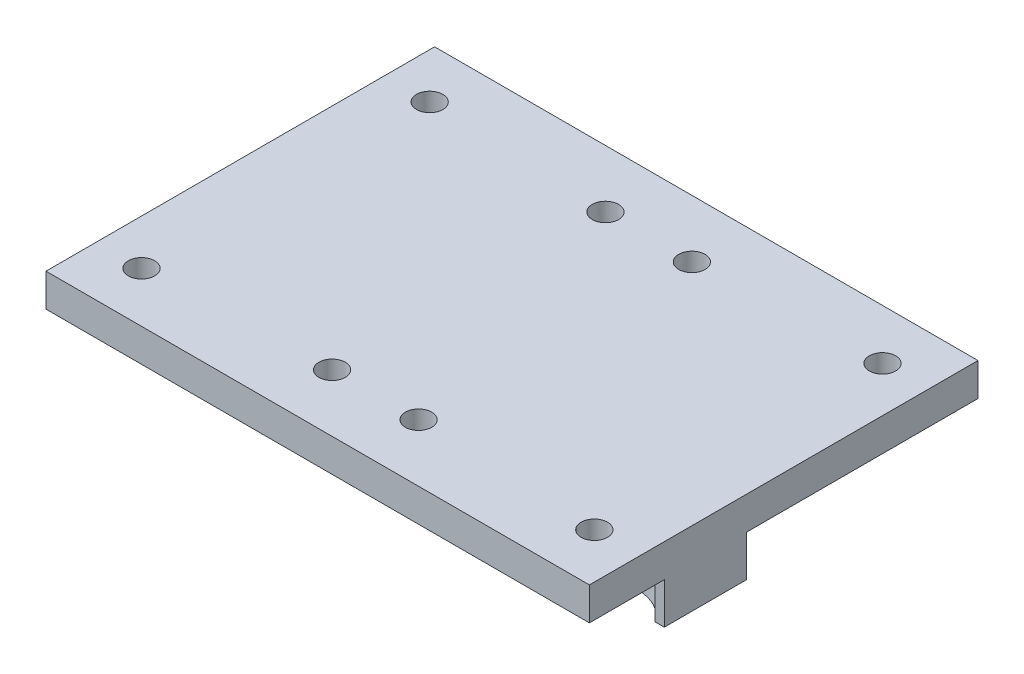
SolidWorks part; units mm, degrees
ref_plane "前视基准面" through (0, 0, 0) normal (0, 0, 1) x (1, 0, 0)
ref_plane "上视基准面" through (0, 0, 0) normal (0, 1, 0) x (1, 0, 0)
ref_plane "右视基准面" through (0, 0, 0) normal (1, 0, 0) x (0, 0, -1)
other "Configuration Table"
sketch "草图7" plane through (0, 0, 0) normal (0, 1, 0) x (1, 0, 0)
  line L21 (0, 23.6) -> (0, -23.6) construction
  line L22 (-33, 23.6) -> (33, 23.6)
  line L23 (-33, 23.6) -> (-33, -23.6)
  line L24 (-33, -23.6) -> (33, -23.6)
  line L25 (33, 23.6) -> (33, -23.6)
  line L26 (-40.0684, 0) -> (37.9065, 0) construction
  line L28 (-33, 14.5) -> (-18, 14.5)
  line L29 (-33, 14.5) -> (-33, 4.5)
  line L30 (-33, 4.5) -> (-18, 4.5)
  line L31 (-18, 14.5) -> (-18, 4.5)
  line L32 (33, -4.5) -> (18, -4.5)
  line L33 (33, -4.5) -> (33, -14.5)
  line L34 (33, -14.5) -> (18, -14.5)
  line L35 (18, -4.5) -> (18, -14.5)
  circle A4 centre (-27.5, 17.5) radius 1.6
  circle A5 centre (27.5, 17.5) radius 1.6
  circle A6 centre (27.5, -17.5) radius 1.6
  circle A7 centre (-27.5, -17.5) radius 1.6
  point P28 (0, 0)
  dimension "D8" = 3.2
  dimension "D3" = 3
  dimension "D4" = 3
  dimension "D6" = 66
  dimension "D7" = 47.2
  dimension "D12" = 55
  dimension "D13" = 35
  dimension "D17" = 10
  dimension "D18" = 15
  dimension "D19" = 15
  dimension "D20" = 10
extrude "凸台-拉伸1" add sketch "草图7" along normal blind 4 contours L35 L32 L25 L22 L23 L28 L31 L30 L24 L34 A5 A4 A6 A7 | L31 L28 L23 L30 | L32 L35 L34 L25 region at (0, 0, 0) region at (-25.5, 0, -9.5) region at (25.5, 0, 9.5)
sketch "草图8" plane through (0, 0, 0) normal (0, -1, 0) x (1, 0, 0)
  line L0 (-5.25, -16.6) -> (5.25, -16.6) construction
  line L1 (0, -16.6) -> (0, -23.6) construction
  line L2 (-37.2445, 0) -> (47.3163, 0) construction
  line L5 (33, 23.6) -> (-33, 23.6)
  line L6 (-33, 23.6) -> (-33, -23.6)
  line L7 (-33, -23.6) -> (33, -23.6)
  line L8 (33, -23.6) -> (33, 23.6)
  line L9 (33, 23.6) -> (-33, 23.6) construction
  line L10 (-33, 23.6) -> (-33, -23.6) construction
  line L11 (-33, -23.6) -> (33, -23.6) construction
  line L12 (33, -23.6) -> (33, 23.6) construction
  circle A0 centre (-5.25, -16.6) radius 1.6
  circle A1 centre (5.25, -16.6) radius 1.6
  circle A2 centre (-5.25, 16.6) radius 1.6
  circle A3 centre (5.25, 16.6) radius 1.6
  dimension "D1" = 3.2
  dimension "D2" = 3.2
  dimension "D3" = 10.5
  dimension "D4" = 0
  dimension "D5" = 7
  dimension "D6" = 33
extrude "切除-拉伸1" cut sketch "草图8" against normal up to surface (4 mm away) up to face at (27.5, 4, -15.9)
extrude "凸台-拉伸2" add sketch "草图7<3>" against normal blind 5 contours L31 L28 L23 L30 | L32 L35 L34 L25 region at (-25.5, 0, -9.5) region at (25.5, 0, 9.5)
sketch "草图7<3>" plane through (0, 0, 0) normal (0, 1, 0) x (1, 0, 0) same geometry as "草图7"
sketch "草图10" plane through (0, 0, 0) normal (0, -1, 0) x (1, 0, 0)
  line L0 (18, 4.5) -> (33, 4.5) construction
  line L1 (33, 4.5) -> (33, 14.5) construction
  line L2 (33, 14.5) -> (18, 14.5) construction
  line L3 (18, 14.5) -> (18, 4.5) construction
  line L4 (-18, -14.5) -> (-18, -4.5) construction
  line L5 (-18, -4.5) -> (-33, -4.5) construction
  line L6 (-33, -4.5) -> (-33, -14.5) construction
  line L7 (-33, -14.5) -> (-18, -14.5) construction
  line L8 (18, 4.5) -> (33, 4.5) construction
  line L9 (33, 4.5) -> (33, 14.5) construction
  line L10 (33, 14.5) -> (18, 14.5) construction
  line L11 (18, 14.5) -> (18, 4.5) construction
  line L12 (-18, -14.5) -> (-18, -4.5) construction
  line L13 (-18, -4.5) -> (-33, -4.5) construction
  line L14 (-33, -4.5) -> (-33, -14.5) construction
  line L15 (-33, -14.5) -> (-18, -14.5) construction
  line L16 (-31.8692, -14.5) -> (-23.1308, -14.5)
  line L17 (31.8692, 14.5) -> (23.1308, 14.5)
  circle A0 centre (27.5, 17.5) radius 1.6 construction
  circle A1 centre (-27.5, -17.5) radius 1.6 construction
  circle A2 centre (27.5, 17.5) radius 1.6 construction
  circle A3 centre (-27.5, -17.5) radius 1.6 construction
  arc A4 (-23.1308, -14.5) -> (-31.8692, -14.5) centre (-27.5, -17.5) ccw
  arc A5 (23.1308, 14.5) -> (31.8692, 14.5) centre (27.5, 17.5) ccw
  point P16 (0, 0)
  point P23 (0, 0)
  line M32 (-18, -14.5) -> (-33, -14.5)
  dimension "D1" = 5.3
  dimension "D2" = 2
extrude "切除-拉伸2" cut sketch "草图10" along normal up to surface (5 mm away) contours A4 M32 | A5 L17 region at (-27.5, 0, -13.5604) up to face at (-25.5, -5, -9.5)
